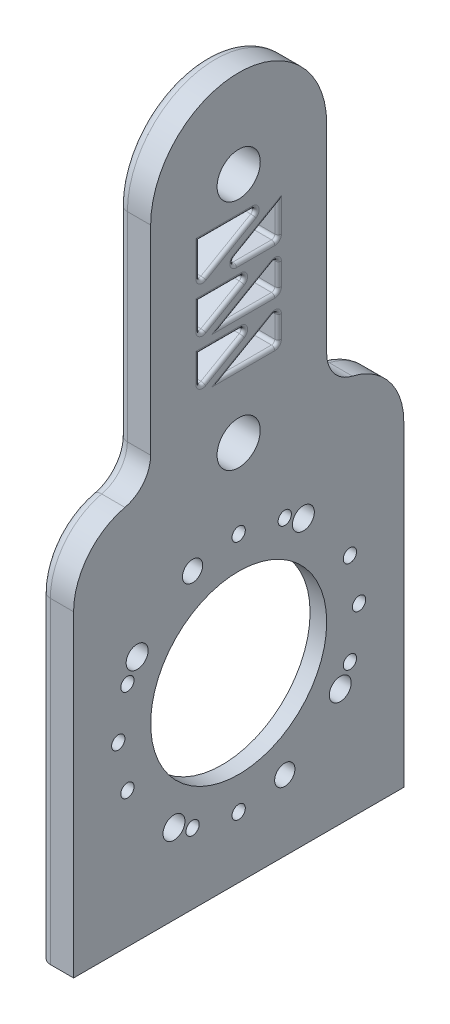
SolidWorks part; units mm, degrees
ref_plane "Front Plane" through (0, 0, 0) normal (0, 0, 1) x (1, 0, 0)
ref_plane "Top Plane" through (0, 0, 0) normal (0, 1, 0) x (1, 0, 0)
ref_plane "Right Plane" through (0, 0, 0) normal (1, 0, 0) x (0, 0, -1)
sketch "Sketch2" plane through (0, 0, 0) normal (1, 0, 0) x (0, 0, -1)
  line L0 (-49.7, 0) -> (-49.7, -54.7)
  line L1 (-49.7, -54.7) -> (49.7, -54.7)
  line L2 (49.7, -54.7) -> (49.7, 30)
  line L3 (0, 0) -> (0, 130) construction
  line L4 (-49.7, 0) -> (-49.7, 130)
  line L6 (49.7, 130) -> (49.7, 30)
  line L7 (-4.0065, 60) -> (3.9935, 60) construction
  line L8 (-49.7, 130) -> (49.7, 130) construction
  arc A0 (-32.0764, 15.2865) -> (-34.9048, 12.4581) centre (-33.4906, 13.8723) ccw
  arc A1 (-34.9048, 12.4581) -> (-32.0764, 15.2865) centre (-33.4906, 13.8723) ccw
  arc A74 (-20.5317, -3.7195) -> (-23.1344, -1.6907) centre (-21.8331, -2.7051) ccw
  arc A75 (-23.1344, -1.6907) -> (-20.5317, -3.7195) centre (-21.8331, -2.7051) ccw
  arc A76 (-16.2541, -14.2736) -> (-18.8568, -12.2448) centre (-17.5554, -13.2592) ccw
  arc A77 (-18.8568, -12.2448) -> (-16.2541, -14.2736) centre (-17.5554, -13.2592) ccw
  arc A78 (-7.2725, -21.275) -> (-9.8752, -19.2461) centre (-8.5738, -20.2605) ccw
  arc A79 (-9.8752, -19.2461) -> (-7.2725, -21.275) centre (-8.5738, -20.2605) ccw
  arc A80 (4.0065, -22.8475) -> (1.4038, -20.8186) centre (2.7051, -21.8331) ccw
  arc A81 (1.4038, -20.8186) -> (4.0065, -22.8475) centre (2.7051, -21.8331) ccw
  arc A82 (14.5606, -18.5698) -> (11.9579, -16.541) centre (13.2592, -17.5554) ccw
  arc A83 (11.9579, -16.541) -> (14.5606, -18.5698) centre (13.2592, -17.5554) ccw
  arc A84 (21.5619, -9.5882) -> (18.9592, -7.5594) centre (20.2605, -8.5738) ccw
  arc A85 (18.9592, -7.5594) -> (21.5619, -9.5882) centre (20.2605, -8.5738) ccw
  arc A86 (23.1344, 1.6907) -> (20.5317, 3.7195) centre (21.8331, 2.7051) ccw
  arc A87 (20.5317, 3.7195) -> (23.1344, 1.6907) centre (21.8331, 2.7051) ccw
  arc A88 (18.8568, 12.2448) -> (16.2541, 14.2736) centre (17.5554, 13.2592) ccw
  arc A89 (16.2541, 14.2736) -> (18.8568, 12.2448) centre (17.5554, 13.2592) ccw
  arc A90 (9.8752, 19.2461) -> (7.2725, 21.275) centre (8.5738, 20.2605) ccw
  arc A91 (7.2725, 21.275) -> (9.8752, 19.2461) centre (8.5738, 20.2605) ccw
  arc A92 (-1.4038, 20.8186) -> (-4.0065, 22.8475) centre (-2.7051, 21.8331) ccw
  arc A93 (-4.0065, 22.8475) -> (-1.4038, 20.8186) centre (-2.7051, 21.8331) ccw
  arc A94 (-11.9579, 16.541) -> (-14.5606, 18.5698) centre (-13.2592, 17.5554) ccw
  arc A95 (-14.5606, 18.5698) -> (-11.9579, 16.541) centre (-13.2592, 17.5554) ccw
  arc A96 (-18.9592, 7.5594) -> (-21.5619, 9.5882) centre (-20.2605, 8.5738) ccw
  arc A97 (-21.5619, 9.5882) -> (-18.9592, 7.5594) centre (-20.2605, 8.5738) ccw
  arc A98 (-17.1437, -28.2395) -> (-21.8106, -32.9064) centre (-19.4771, -30.5729) ccw
  arc A99 (-21.8106, -32.9064) -> (-17.1437, -28.2395) centre (-19.4771, -30.5729) ccw
  arc A102 (32.9064, -17.1437) -> (28.2395, -21.8106) centre (30.5729, -19.4771) ccw
  arc A103 (28.2395, -21.8106) -> (32.9064, -17.1437) centre (30.5729, -19.4771) ccw
  arc A104 (21.8106, 32.9064) -> (17.1437, 28.2395) centre (19.4771, 30.5729) ccw
  arc A105 (17.1437, 28.2395) -> (21.8106, 32.9064) centre (19.4771, 30.5729) ccw
  arc A108 (-28.2395, 21.8106) -> (-32.9064, 17.1437) centre (-30.5729, 19.4771) ccw
  arc A109 (-32.9064, 17.1437) -> (-28.2395, 21.8106) centre (-30.5729, 19.4771) ccw
  arc A110 (-20.9002, 16.2921) -> (20.9002, -16.2921) centre (0, 0) ccw
  arc A111 (20.9002, -16.2921) -> (-20.9002, 16.2921) centre (0, 0) ccw
  circle A112 centre (0, 0) radius 40.5
  arc A113 (16.029, -31.334) -> (11.7156, -35.6473) centre (13.8723, -33.4906) ccw
  arc A114 (-37.6642, -1.4142) -> (-34.8358, 1.4142) centre (-36.25, 0) ccw
  arc A115 (-34.8358, 1.4142) -> (-37.6642, -1.4142) centre (-36.25, 0) ccw
  arc A116 (-34.9048, -15.2865) -> (-32.0764, -12.4581) centre (-33.4906, -13.8723) ccw
  arc A117 (-32.0764, -12.4581) -> (-34.9048, -15.2865) centre (-33.4906, -13.8723) ccw
  arc A118 (-12.4581, -32.0764) -> (-15.2865, -34.9048) centre (-13.8723, -33.4906) ccw
  arc A119 (-15.2865, -34.9048) -> (-12.4581, -32.0764) centre (-13.8723, -33.4906) ccw
  arc A120 (-1.4142, -37.6642) -> (1.4142, -34.8358) centre (0, -36.25) ccw
  arc A121 (1.4142, -34.8358) -> (-1.4142, -37.6642) centre (0, -36.25) ccw
  arc A122 (32.0764, -15.2865) -> (34.9048, -12.4581) centre (33.4906, -13.8723) ccw
  arc A123 (34.9048, -12.4581) -> (32.0764, -15.2865) centre (33.4906, -13.8723) ccw
  arc A124 (34.8358, -1.4142) -> (37.6642, 1.4142) centre (36.25, 0) ccw
  arc A125 (37.6642, 1.4142) -> (34.8358, -1.4142) centre (36.25, 0) ccw
  arc A126 (32.0764, 12.4581) -> (34.9048, 15.2865) centre (33.4906, 13.8723) ccw
  arc A127 (34.9048, 15.2865) -> (32.0764, 12.4581) centre (33.4906, 13.8723) ccw
  arc A128 (15.2865, 34.9048) -> (12.4581, 32.0764) centre (13.8723, 33.4906) ccw
  arc A129 (12.4581, 32.0764) -> (15.2865, 34.9048) centre (13.8723, 33.4906) ccw
  arc A130 (-1.4142, 34.8358) -> (1.4142, 37.6642) centre (0, 36.25) ccw
  arc A131 (1.4142, 37.6642) -> (-1.4142, 34.8358) centre (0, 36.25) ccw
  arc A134 (11.7156, -35.6473) -> (16.029, -31.334) centre (13.8723, -33.4906) ccw
  arc A135 (-16.029, 31.334) -> (-11.7156, 35.6473) centre (-13.8723, 33.4906) ccw
  arc A136 (-11.7156, 35.6473) -> (-16.029, 31.334) centre (-13.8723, 33.4906) ccw
  arc A137 (49.7, 130) -> (-49.7, 130) centre (0, 130) ccw
  circle A138 centre (-0.0065, 60) radius 6.5
  circle A139 centre (0, 130) radius 6.5
  dimension "D1" = 130
  dimension "D2" = 54.7
  dimension "D3" = 70
extrude "Boss-Extrude1" add sketch "Sketch2" along normal blind 5 contours A112 A131 A130 A129 A128 A127 A126 A125 A124 A123 A122 A121 A120 A119 A118 A117 A116 A115 A114 A1 A0 A99 A98 A103 A102 A105 A104 A109 A108 A111 | L4 A112 region at (0, 74.4467, -0.0001) region at (0, 0, 39.3545)
extrude "Boss-Extrude2" add sketch "Sketch2<5>" against normal blind 5 contours L4 A112 region at (0, 74.4467, -0.0001)
sketch "Sketch2<5>" plane through (0, 0, 0) normal (1, 0, 0) x (0, 0, -1) same geometry as "Sketch2"
ref_plane "Plane1" through (0, -54.7, 0) normal (0, -1, 0) x (-1, 0, 0)
sketch "Sketch3" plane through (0, -54.7, 0) normal (0, -1, 0) x (-1, 0, 0)
  line L0 (-5, 0) -> (35, 0) construction
  line L1 (-5, 55) -> (35, 55)
  line L2 (-5, 55) -> (-5, -55)
  line L3 (-5, -55) -> (35, -55)
  line L5 (35, -55) -> (35, 0)
  line L6 (35, 55) -> (35, 0)
  dimension "D1" = 40
  dimension "D2" = 55
sketch "Sketch7" plane through (5, 0, 0) normal (1, 0, 0) x (0, 0, -1)
  arc A0 (-32.0764, 15.2865) -> (-34.9048, 12.4581) centre (-33.4906, 13.8723) ccw
  arc A1 (-34.9048, 12.4581) -> (-32.0764, 15.2865) centre (-33.4906, 13.8723) ccw
  arc A2 (-20.5317, -3.7195) -> (-23.1344, -1.6907) centre (-21.8331, -2.7051) ccw
  arc A3 (-23.1344, -1.6907) -> (-20.5317, -3.7195) centre (-21.8331, -2.7051) ccw
  arc A4 (-16.2541, -14.2736) -> (-18.8568, -12.2448) centre (-17.5554, -13.2592) ccw
  arc A5 (-18.8568, -12.2448) -> (-16.2541, -14.2736) centre (-17.5554, -13.2592) ccw
  arc A6 (-7.2725, -21.275) -> (-9.8752, -19.2461) centre (-8.5738, -20.2605) ccw
  arc A7 (-9.8752, -19.2461) -> (-7.2725, -21.275) centre (-8.5738, -20.2605) ccw
  arc A8 (4.0065, -22.8475) -> (1.4038, -20.8186) centre (2.7051, -21.8331) ccw
  arc A9 (1.4038, -20.8186) -> (4.0065, -22.8475) centre (2.7051, -21.8331) ccw
  arc A10 (14.5606, -18.5698) -> (11.9579, -16.541) centre (13.2592, -17.5554) ccw
  arc A11 (11.9579, -16.541) -> (14.5606, -18.5698) centre (13.2592, -17.5554) ccw
  arc A12 (21.5619, -9.5882) -> (18.9592, -7.5594) centre (20.2605, -8.5738) ccw
  arc A13 (18.9592, -7.5594) -> (21.5619, -9.5882) centre (20.2605, -8.5738) ccw
  arc A14 (23.1344, 1.6907) -> (20.5317, 3.7195) centre (21.8331, 2.7051) ccw
  arc A15 (20.5317, 3.7195) -> (23.1344, 1.6907) centre (21.8331, 2.7051) ccw
  arc A16 (18.8568, 12.2448) -> (16.2541, 14.2736) centre (17.5554, 13.2592) ccw
  arc A17 (16.2541, 14.2736) -> (18.8568, 12.2448) centre (17.5554, 13.2592) ccw
  arc A18 (9.8752, 19.2461) -> (7.2725, 21.275) centre (8.5738, 20.2605) ccw
  arc A19 (7.2725, 21.275) -> (9.8752, 19.2461) centre (8.5738, 20.2605) ccw
  arc A20 (-1.4038, 20.8186) -> (-4.0065, 22.8475) centre (-2.7051, 21.8331) ccw
  arc A21 (-4.0065, 22.8475) -> (-1.4038, 20.8186) centre (-2.7051, 21.8331) ccw
  arc A22 (-11.9579, 16.541) -> (-14.5606, 18.5698) centre (-13.2592, 17.5554) ccw
  arc A23 (-14.5606, 18.5698) -> (-11.9579, 16.541) centre (-13.2592, 17.5554) ccw
  arc A24 (-18.9592, 7.5594) -> (-21.5619, 9.5882) centre (-20.2605, 8.5738) ccw
  arc A25 (-21.5619, 9.5882) -> (-18.9592, 7.5594) centre (-20.2605, 8.5738) ccw
  arc A26 (-17.1437, -28.2395) -> (-21.8106, -32.9064) centre (-19.4771, -30.5729) ccw
  arc A27 (-21.8106, -32.9064) -> (-17.1437, -28.2395) centre (-19.4771, -30.5729) ccw
  arc A28 (32.9064, -17.1437) -> (28.2395, -21.8106) centre (30.5729, -19.4771) ccw
  arc A29 (28.2395, -21.8106) -> (32.9064, -17.1437) centre (30.5729, -19.4771) ccw
  arc A30 (21.8106, 32.9064) -> (17.1437, 28.2395) centre (19.4771, 30.5729) ccw
  arc A31 (17.1437, 28.2395) -> (21.8106, 32.9064) centre (19.4771, 30.5729) ccw
  arc A32 (-28.2395, 21.8106) -> (-32.9064, 17.1437) centre (-30.5729, 19.4771) ccw
  arc A33 (-32.9064, 17.1437) -> (-28.2395, 21.8106) centre (-30.5729, 19.4771) ccw
  arc A34 (-20.9002, 16.2921) -> (20.9002, -16.2921) centre (0, 0) ccw
  arc A35 (20.9002, -16.2921) -> (-20.9002, 16.2921) centre (0, 0) ccw
  circle A36 centre (0, 0) radius 40.5
  arc A37 (16.029, -31.334) -> (11.7156, -35.6473) centre (13.8723, -33.4906) ccw
  arc A38 (-37.6642, -1.4142) -> (-34.8358, 1.4142) centre (-36.25, 0) ccw
  arc A39 (-34.8358, 1.4142) -> (-37.6642, -1.4142) centre (-36.25, 0) ccw
  arc A40 (-34.9048, -15.2865) -> (-32.0764, -12.4581) centre (-33.4906, -13.8723) ccw
  arc A41 (-32.0764, -12.4581) -> (-34.9048, -15.2865) centre (-33.4906, -13.8723) ccw
  arc A42 (-12.4581, -32.0764) -> (-15.2865, -34.9048) centre (-13.8723, -33.4906) ccw
  arc A43 (-15.2865, -34.9048) -> (-12.4581, -32.0764) centre (-13.8723, -33.4906) ccw
  arc A44 (-1.4142, -37.6642) -> (1.4142, -34.8358) centre (0, -36.25) ccw
  arc A45 (1.4142, -34.8358) -> (-1.4142, -37.6642) centre (0, -36.25) ccw
  arc A46 (32.0764, -15.2865) -> (34.9048, -12.4581) centre (33.4906, -13.8723) ccw
  arc A47 (34.9048, -12.4581) -> (32.0764, -15.2865) centre (33.4906, -13.8723) ccw
  arc A48 (34.8358, -1.4142) -> (37.6642, 1.4142) centre (36.25, 0) ccw
  arc A49 (37.6642, 1.4142) -> (34.8358, -1.4142) centre (36.25, 0) ccw
  arc A50 (32.0764, 12.4581) -> (34.9048, 15.2865) centre (33.4906, 13.8723) ccw
  arc A51 (34.9048, 15.2865) -> (32.0764, 12.4581) centre (33.4906, 13.8723) ccw
  arc A52 (15.2865, 34.9048) -> (12.4581, 32.0764) centre (13.8723, 33.4906) ccw
  arc A53 (12.4581, 32.0764) -> (15.2865, 34.9048) centre (13.8723, 33.4906) ccw
  arc A54 (-1.4142, 34.8358) -> (1.4142, 37.6642) centre (0, 36.25) ccw
  arc A55 (1.4142, 37.6642) -> (-1.4142, 34.8358) centre (0, 36.25) ccw
  arc A56 (35.1432, 35.1432) -> (-35.1432, -35.1432) centre (0, 0) ccw
  arc A57 (-35.1432, -35.1432) -> (35.1432, 35.1432) centre (0, 0) ccw
  arc A58 (11.7156, -35.6473) -> (16.029, -31.334) centre (13.8723, -33.4906) ccw
  arc A59 (-16.029, 31.334) -> (-11.7156, 35.6473) centre (-13.8723, 33.4906) ccw
  arc A60 (-11.7156, 35.6473) -> (-16.029, 31.334) centre (-13.8723, 33.4906) ccw
sketch "Sketch8" plane through (5, 0, 0) normal (1, 0, 0) x (0, 0, -1)
  line L0 (-0.0065, 60) -> (49.7, 60) construction
  line L1 (26.5, 130) -> (26.5, 60) construction
  line L2 (0, 130) -> (-0.0065, 60) construction
  line L3 (49.7, -54.7) -> (49.7, 130)
  line L4 (-49.7, 130) -> (-49.7, -54.7)
  line L5 (-49.7, -54.7) -> (49.7, -54.7)
  line L6 (49.7, -54.7) -> (49.7, 130)
  line L7 (-49.7, 130) -> (-49.7, -54.7)
  line L8 (-49.7, -54.7) -> (49.7, -54.7)
  line L9 (26.5, 130) -> (26.5, 60)
  line L10 (26.5, 60) -> (49.7, 60)
  line L11 (-26.5129, 60.0049) -> (-49.7129, 60.0092)
  line L12 (-26.5, 130.0049) -> (-26.5129, 60.0049)
  circle A0 centre (-0.0065, 60) radius 6.5 construction
  arc A1 (49.7, 130) -> (-49.7, 130) centre (0, 130) ccw
  arc A2 (49.7, 130) -> (-49.7, 130) centre (0, 130) ccw
  circle A3 centre (0, 130) radius 6.5 construction
  circle A4 centre (-0.0065, 60) radius 6.5
  circle A5 centre (0, 130) radius 6.5
  arc A6 (26.5, 130) -> (-26.5, 130.0049) centre (0, 130) ccw
  circle A7 centre (0, 130) radius 26.5 construction
  arc M31 (49.7, 130) -> (-49.7, 130) centre (0, 130) ccw
  line M32 (-49.7, 130) -> (-49.7, -54.7)
  dimension "D1" = 0
  dimension "D2" = 20
extrude "Cut-Extrude10" cut sketch "Sketch8" against normal blind 10 contours A6 L9 L10 L6 L11 L12 M31 M32 region at (5, 61.5559, -38.1)
fillet "Fillet1" radius 10 2 edges at (0, 60.0049, 26.5129) (0, 60, -26.5)
fillet "Fillet2" radius 20 2 edges at (0, 60.0092, 49.7) (0, 60, -49.7)
fillet "Fillet3" radius 1 1 edges at (-5, 0, -40.5)
fillet "Fillet4" radius 3 9 edges at (-5, -6.9596, -49.7) (-5, 53.2173, -45.3631) (-5, 63.7817, -28.6684) (-5, 100, -26.5) (-5, -6.9549, 49.7) (-5, 53.2237, 45.3655) (-5, 63.7892, 28.6789) (-5, 100.0049, 26.5055) (-5, 156.5, -0.0024)
sketch "Sketch9" plane through (-5, 0, 0) normal (-1, 0, 0) x (0, 0, 1)
  line L0 (0, 130) -> (0, 118.6831) construction
  line L1 (-11.8762, 118.6831) -> (11.8762, 118.6831)
  line L2 (-11.8762, 118.6831) -> (-11.8762, 71.3169)
  line L3 (-11.8762, 71.3169) -> (11.8762, 71.3169)
  line L4 (11.8762, 118.6831) -> (11.8762, 71.3169)
  line L5 (-11.8762, 118.6831) -> (11.8762, 104.9696)
  line L6 (11.8762, 104.9696) -> (-11.8762, 104.9696)
  line L7 (-11.8762, 104.9696) -> (11.8762, 91.2562)
  line L8 (11.8762, 91.2562) -> (-11.8762, 91.2562)
  line L9 (-11.8762, 91.2562) -> (11.8762, 77.5427)
  line L10 (11.8762, 77.5427) -> (-11.8762, 77.5427)
  line L11 (-11.8762, 77.5427) -> (-0.0004, 70.6861)
  line L12 (-11.8762, 116.3737) -> (4.4121, 106.9696)
  line L13 (4.4121, 106.9696) -> (-11.8762, 106.9696)
  line L14 (-11.8762, 102.6602) -> (4.4121, 93.2562)
  line L15 (4.4121, 93.2562) -> (-11.8762, 93.2562)
  line L16 (-11.8762, 88.9468) -> (4.4121, 79.5427)
  line L17 (4.4121, 79.5427) -> (-11.8762, 79.5427)
  line L18 (-11.8762, 75.2333) -> (-5.0928, 71.3169)
  line L19 (-7.8762, 118.6831) -> (11.8762, 107.279)
  line L20 (11.8762, 102.9696) -> (-4.4121, 102.9696)
  line L21 (-4.4121, 102.9696) -> (11.8762, 93.5656)
  line L22 (11.8762, 89.2562) -> (-4.4121, 89.2562)
  line L23 (-4.4121, 89.2562) -> (11.8762, 79.8521)
  line L24 (11.8762, 75.5427) -> (-4.4121, 75.5427)
  line L25 (-4.4121, 75.5427) -> (2.9072, 71.3169)
  line L26 (-0.0004, 70.6861) -> (0, 71.3169) construction
  point P0 (8.8533, 91.3721)
  point P37 (0, 130)
extrude "Cut-Extrude11" cut sketch "Sketch9" against normal blind 10 contours L13 L12 L2 | L1 L19 L4 | L20 L21 L4 | L22 L23 L4 | L15 L14 L2 | L17 L16 L2 region at (-5, 114.8818, 5.2921) region at (-5, 110.1043, -6.4468) region at (-5, 99.8349, 6.4468) region at (-5, 96.3909, -6.4468) region at (-5, 86.1215, 6.4468) region at (-5, 82.6774, -6.4468)
fillet "Fillet5" radius 1 48 edges at (5, 118.6831, 2) (-5, 118.6831, 2) (5, 112.9811, 11.8762) (-5, 112.9811, 11.8762) (5, 111.6717, -11.8762) (-5, 111.6717, -11.8762) (5, 111.6717, -3.7321) (-5, 111.6717, -3.7321) (5, 102.9696, 3.7321) (-5, 102.9696, 3.7321) (5, 98.2676, 11.8762) (-5, 98.2676, 11.8762) (5, 89.2562, 3.7321) (-5, 89.2562, 3.7321) (5, 84.5541, 11.8762) (-5, 84.5541, 11.8762) (5, 97.9582, -3.7321) (-5, 97.9582, -3.7321) (5, 93.2562, -3.7321) (-5, 93.2562, -3.7321) (5, 84.2447, -3.7321) (-5, 84.2447, -3.7321) (5, 79.5427, -3.7321) (-5, 79.5427, -3.7321) (0, 118.6831, -7.8762) (5, 112.9811, 2) (0, 107.279, 11.8762) (-5, 112.9811, 2) (0, 106.9696, -11.8762) (5, 106.9696, -3.7321) (0, 106.9696, 4.4121) (-5, 106.9696, -3.7321) (0, 102.9696, -4.4121) (5, 98.2676, 3.7321) (0, 93.5656, 11.8762) (-5, 98.2676, 3.7321) (0, 89.2562, -4.4121) (5, 84.5541, 3.7321) (0, 79.8521, 11.8762) (-5, 84.5541, 3.7321) (0, 102.6602, -11.8762) (5, 97.9582, -11.8762) (0, 93.2562, -11.8762) (-5, 97.9582, -11.8762) (0, 88.9468, -11.8762) (5, 84.2447, -11.8762) (0, 79.5427, -11.8762) (-5, 84.2447, -11.8762)
